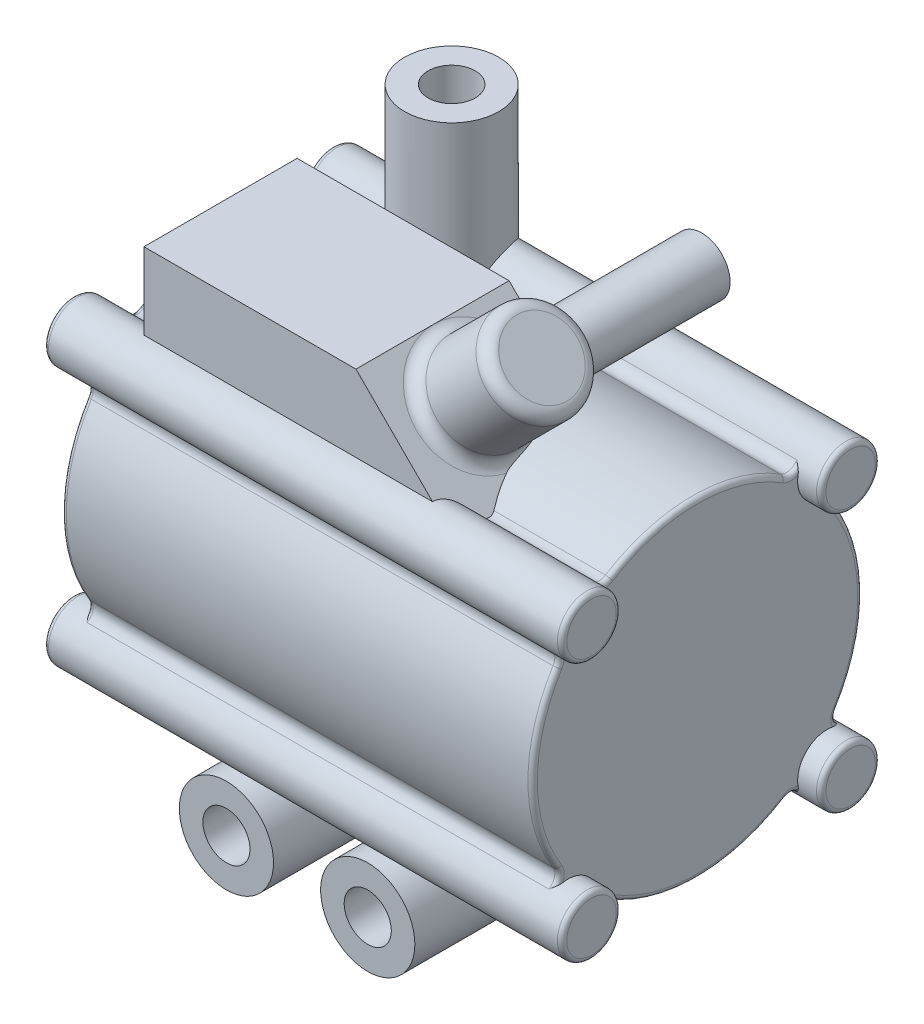
SolidWorks part; units mm, degrees
material "1060 Alloy"
ref_plane "Front Plane" through (0, 0, 0) normal (0, 0, 1) x (1, 0, 0)
ref_plane "Top Plane" through (0, 0, 0) normal (0, 1, 0) x (1, 0, 0)
ref_plane "Right Plane" through (0, 0, 0) normal (1, 0, 0) x (0, 0, -1)
sketch "Sketch1" plane through (0, 0, 0) normal (1, 0, 0) x (0, 0, -1)
  line L1 (27.5, 27.5) -> (-27.5, 27.5) construction
  line L2 (27.5, 27.5) -> (27.5, -27.5) construction
  line L3 (27.5, -27.5) -> (-27.5, -27.5) construction
  line L4 (-27.5, 27.5) -> (-27.5, -27.5) construction
  arc A0 (18.553, 29.678) -> (-18.553, 29.678) centre (0, 0) ccw
  arc A1 (-22.0559, 30.5699) -> (-30.5699, 22.0559) centre (-27.5, 27.5) ccw
  arc A2 (30.5699, 22.0559) -> (22.0559, 30.5699) centre (27.5, 27.5) ccw
  arc A3 (-30.5699, -22.0559) -> (-22.0559, -30.5699) centre (-27.5, -27.5) ccw
  arc A4 (22.0559, -30.5699) -> (30.5699, -22.0559) centre (27.5, -27.5) ccw
  arc A5 (-29.678, 18.553) -> (-29.678, -18.553) centre (0, 0) ccw
  arc A6 (-18.553, -29.678) -> (18.553, -29.678) centre (0, 0) ccw
  arc A7 (29.678, -18.553) -> (29.678, 18.553) centre (0, 0) ccw
  arc A8 (29.678, 18.553) -> (30.5699, 22.0559) centre (31.7979, 19.8783) cw
  arc A9 (30.5699, -22.0559) -> (29.678, -18.553) centre (31.7979, -19.8783) cw
  arc A10 (18.553, -29.678) -> (22.0559, -30.5699) centre (19.8783, -31.7979) cw
  arc A11 (-18.553, -29.678) -> (-22.0559, -30.5699) centre (-19.8783, -31.7979) ccw
  arc A12 (-29.678, -18.553) -> (-30.5699, -22.0559) centre (-31.7979, -19.8783) cw
  arc A13 (-30.5699, 22.0559) -> (-29.678, 18.553) centre (-31.7979, 19.8783) cw
  arc A14 (-22.0559, 30.5699) -> (-18.553, 29.678) centre (-19.8783, 31.7979) ccw
  arc A15 (18.553, 29.678) -> (22.0559, 30.5699) centre (19.8783, 31.7979) ccw
  point P3 (0, 0)
  point P9 (0, 27.5)
  point P11 (0, 0)
  point P14 (0, 0)
  point P15 (27.5, 0)
  point P23 (27.8051, -21.2574)
  point P32 (-27.8051, 21.2574)
  dimension "D1" = 70
  dimension "D2" = 12.5
  dimension "D4" = 2.5
  dimension "D3" = 55
extrude "Boss-Extrude1" add sketch "Sketch1" against normal blind 50 and the other way blind 50
sketch "Sketch2" plane through (0, 0, 0) normal (1, 0, 0) x (0, 0, -1)
  circle A0 centre (-27.5, 27.5) radius 6.25
  circle A1 centre (27.5, 27.5) radius 6.25
  circle A2 centre (27.5, -27.5) radius 6.25
  circle A3 centre (-27.5, -27.5) radius 6.25
extrude "Boss-Extrude2" add sketch "Sketch2" along normal blind 55 and the other way blind 55
fillet "Fillet1" radius 1 8 edges at (-55, -27.5, 21.25) (-55, -27.5, -33.75) (-55, 27.5, 21.25) (-55, 27.5, -33.75) (55, -27.5, 21.25) (55, -27.5, -33.75) (55, 27.5, -33.75) (55, 27.5, 21.25)
fillet "Fillet2" radius 1 24 edges at (50, -20.4951, -29.3752) (50, 20.4951, -29.3752) (50, -29.3752, 20.4951) (50, -29.3752, -20.4951) (50, 20.4951, 29.3752) (50, -20.4951, 29.3752) (50, 29.3752, -20.4951) (50, 29.3752, 20.4951) (-50, -29.3752, 20.4951) (-50, -29.3752, -20.4951) (-50, -20.4951, -29.3752) (-50, 20.4951, -29.3752) (-50, 29.3752, -20.4951) (-50, 29.3752, 20.4951) (-50, 20.4951, 29.3752) (-50, -20.4951, 29.3752) (50, 0, -35) (50, -35, 0) (50, 0, 35) (50, 35, 0) (-50, -35, 0) (-50, 0, -35) (-50, 35, 0) (-50, 0, 35)
sketch "Sketch3" plane through (0, 0, 0) normal (0, 0, 1) x (1, 0, 0)
  circle A0 centre (15, -42) radius 5
  circle A1 centre (-15, -42) radius 5
  circle A2 centre (15, -42) radius 10
  circle A3 centre (-15, -42) radius 10
  point P6 (0, 0)
  dimension "D3" = 20
  dimension "D4" = 10
  dimension "D1" = 15
  dimension "D2" = 15
  dimension "D5" = 42
extrude "Boss-Extrude3" add sketch "Sketch3" along normal blind 35 and the other way blind 35
sketch "Sketch4" plane through (0, 0, 0) normal (0, 1, 0) x (1, 0, 0)
  circle A0 centre (-27.1824, 25) radius 10
  circle A1 centre (-27.1824, 25) radius 5
  dimension "D2" = 10
  dimension "D3" = 20
  dimension "D1" = 25
extrude "Boss-Extrude5" add sketch "Sketch4" along normal blind 60
sketch "Sketch7" plane through (0, 0, 0) normal (0, 0, 1) x (1, 0, 0)
  line L0 (-40, 25) -> (-40, 50)
  line L1 (-40, 50) -> (5, 50)
  line L2 (5, 50) -> (30, 25)
  line L3 (30, 25) -> (-40, 25)
  dimension "D1" = 45
  dimension "D2" = 25
  dimension "D3" = 25
  dimension "D4" = 70
  dimension "D5" = 40
extrude "Boss-Extrude6" add sketch "Sketch7" along normal blind 27.5 and the other way blind 5
sketch "Sketch8" plane through (27.5, 27.5, 0) normal (0.7071, 0.7071, 0) x (0, 0, -1)
  line L0 (5, 31.8198) -> (-27.5, 31.8198) construction
  line L1 (5, 10.0989) -> (5, 31.8198) construction
  circle A0 centre (-11, 19.3198) radius 10
  dimension "D1" = 20
  dimension "D2" = 12.5
  dimension "D3" = 16
extrude "Boss-Extrude7" add sketch "Sketch8" along normal blind 20
sketch "Sketch9" plane through (0, 0, 0) normal (0, 0, 1) x (1, 0, 0)
  line L0 (20.9099, 62.3744) -> (6.7678, 48.2322) construction
  line L1 (35.052, 48.2322) -> (20.9099, 62.3744) construction
  circle A0 centre (20.9099, 48.2322) radius 6
  circle A1 centre (20.9099, 48.2322) radius 4
  dimension "D1" = 10
  dimension "D2" = 10
  dimension "D3" = 12
  dimension "D4" = 8
extrude "Boss-Extrude8" add sketch "Sketch9" along normal blind 10 and the other way blind 30
fillet "Fillet3" radius 2.5 2 edges at (6.7678, 48.2322, 11) (20.9099, 62.3744, 11)
sketch "Sketch10" plane through (-50, 0, 0) normal (-1, 0, 0) x (0, 0, 1)
  circle A0 centre (0, 0) radius 7.5
  dimension "D1" = 15
extrude "Cut-Extrude1" cut sketch "Sketch10" against normal blind 20
